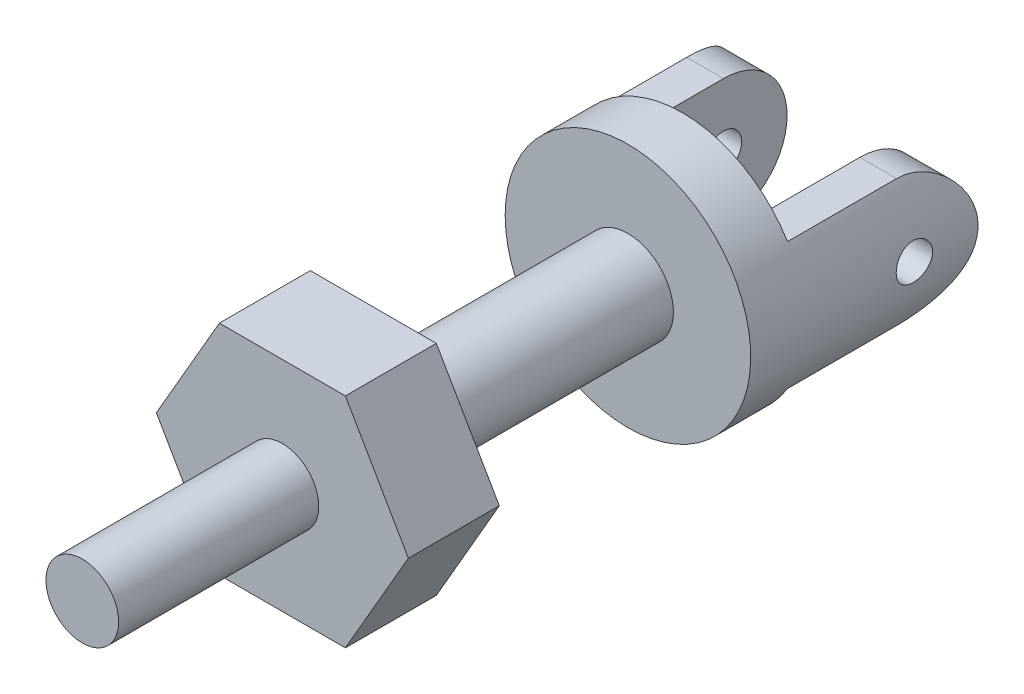
SolidWorks part; units mm, degrees
ref_plane "Front Plane" through (0, 0, 0) normal (0, 0, 1) x (1, 0, 0)
ref_plane "Top Plane" through (0, 0, 0) normal (0, 1, 0) x (1, 0, 0)
ref_plane "Right Plane" through (0, 0, 0) normal (1, 0, 0) x (0, 0, -1)
sketch "Sketch2" plane through (0, 0, 0) normal (0, 0, 1) x (1, 0, 0)
  line L1 (3.4641, -6) -> (6.9282, 0)
  line L2 (6.9282, 0) -> (3.4641, 6)
  line L3 (3.4641, 6) -> (-3.4641, 6)
  line L4 (-3.4641, 6) -> (-6.9282, 0)
  line L5 (-6.9282, 0) -> (-3.4641, -6)
  line L6 (-3.4641, -6) -> (3.4641, -6)
  circle A0 centre (0, 0) radius 6 construction
  dimension "D1" = 12
extrude "Hexagon" add sketch "Sketch2" along normal blind 5
sketch "Sketch3" plane through (0, 0, 5) normal (0, 0, 1) x (1, 0, 0)
  circle A0 centre (0, 0) radius 2
  dimension "D1" = 4
extrude "Screw Post" add sketch "Sketch3" along normal blind 11
sketch "Sketch4" plane through (0, 0, 0) normal (0, 0, -1) x (-1, 0, 0)
  circle A0 centre (0, 0) radius 2.5
  dimension "D1" = 5
extrude "Bearing Section" add sketch "Sketch4" along normal blind 14
sketch "Sketch5" plane through (0, 0, -14) normal (0, 0, -1) x (-1, 0, 0)
  circle A0 centre (0, 0) radius 6.75
  dimension "D1" = 13.5
extrude "U Joint Base" add sketch "Sketch5" along normal blind 3
sketch "Sketch6" plane through (0, 0, -17) normal (0, 0, -1) x (-1, 0, 0)
  line L0 (-5.7717, 3.5) -> (-3.75, 3.5)
  line L1 (-3.75, 3.5) -> (-3.75, -3.5)
  line L2 (-3.75, -3.5) -> (-5.7717, -3.5)
  line L3 (3.75, -3.5) -> (3.75, 3.5)
  line L4 (3.75, 3.5) -> (5.7717, 3.5)
  line L5 (5.7717, -3.5) -> (3.75, -3.5)
  circle A0 centre (0, 0) radius 6.75 construction
  arc A1 (-5.7717, 3.5) -> (-5.7717, -3.5) centre (0, 0) ccw
  arc A2 (5.7717, -3.5) -> (5.7717, 3.5) centre (0, 0) ccw
  point P16 (0, 0)
  dimension "D2" = 7.5
  dimension "D3" = 7
  dimension "D1" = 2
extrude "U Joint Standups" add sketch "Sketch6" along normal blind 9.5
sketch "Sketch7" plane through (0, 0, 0) normal (1, 0, 0) x (0, 0, -1)
  line L0 (23, 3.5) -> (26.5, 3.5)
  line L1 (26.5, 3.5) -> (17, 3.5) construction
  line L2 (26.5, 3.5) -> (26.5, -3.5)
  line L4 (-5, 0) -> (0, 0) construction
  line L5 (23, -3.5) -> (26.5, -3.5)
  arc A0 (23, -3.5) -> (23, 3.5) centre (23, 0) ccw
extrude "Standup Round" cut sketch "Sketch7" against normal through all both and the other way through all contours A0 L5 L2 | A0 L2 L0 | A0 L0 L2 L5 region at (0, -2.7182, -25.7182) region at (0, 2.7182, -25.7182)
sketch "Sketch8" plane through (0, 0, 0) normal (1, 0, 0) x (0, 0, -1)
  circle A0 centre (23, 0) radius 1
  arc A1 (23, -3.5) -> (23, 3.5) centre (23, 0) ccw construction
  dimension "D1" = 2
extrude "Ball Holes" cut sketch "Sketch8" against normal through all both and the other way through all
